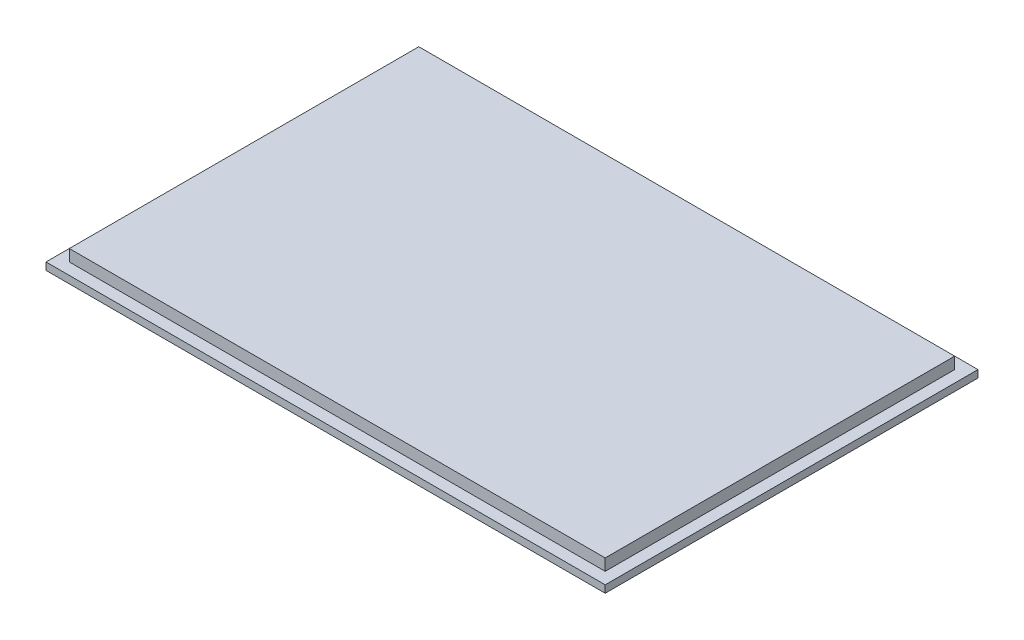
SolidWorks part; units mm, degrees
ref_plane "Front Plane" through (0, 0, 0) normal (0, 0, 1) x (1, 0, 0)
ref_plane "Top Plane" through (0, 0, 0) normal (0, 1, 0) x (1, 0, 0)
ref_plane "Right Plane" through (0, 0, 0) normal (1, 0, 0) x (0, 0, -1)
sketch "Sketch1" plane through (0, 0, 0) normal (0, 1, 0) x (1, 0, 0)
  line L1 (-89.7367, 52.2671) -> (62.6633, 52.2671)
  line L2 (-89.7367, 52.2671) -> (-89.7367, -49.3329)
  line L3 (-89.7367, -49.3329) -> (62.6633, -49.3329)
  line L4 (62.6633, 52.2671) -> (62.6633, -49.3329)
  line L5 (-86.5617, 49.0921) -> (59.4883, 49.0921)
  line L6 (-86.5617, 49.0921) -> (-86.5617, -46.1579)
  line L7 (-86.5617, -46.1579) -> (59.4883, -46.1579)
  line L8 (59.4883, 49.0921) -> (59.4883, -46.1579)
  dimension "D1" = 101.6
  dimension "D2" = 152.4
  dimension "D3" = 95.25
  dimension "D4" = 146.05
  dimension "D5" = 3.175
  dimension "D6" = 3.175
extrude "Boss-Extrude1" add sketch "Sketch1" along normal blind 2 contours L2 L3 L4 L1
extrude "Boss-Extrude2" add sketch "Sketch1<3>" along normal blind 5.175 contours L8 L5 L6 L7 region at (-13.5367, 0, -1.4671)
sketch "Sketch1<3>" plane through (0, 0, 0) normal (0, 1, 0) x (1, 0, 0) same geometry as "Sketch1"
